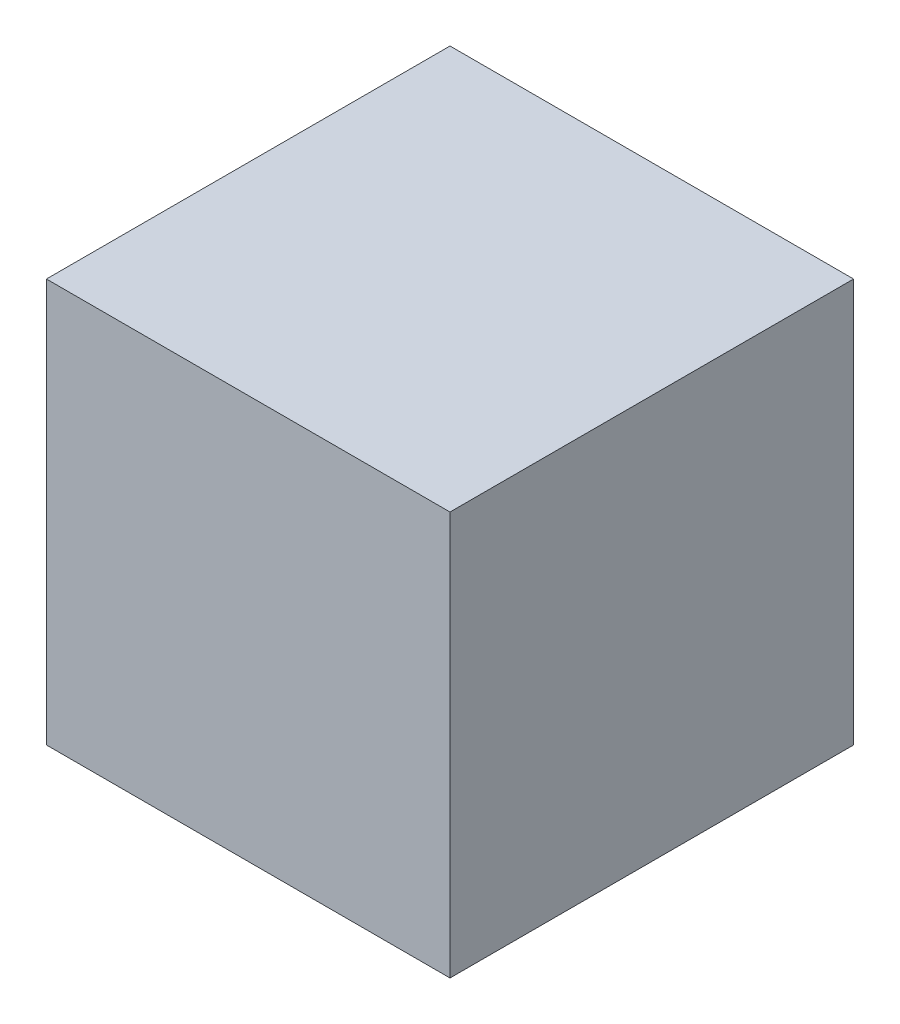
SolidWorks part; units mm, degrees
ref_plane "Front Plane" through (0, 0, 0) normal (0, 0, 1) x (1, 0, 0)
ref_plane "Top Plane" through (0, 0, 0) normal (0, 1, 0) x (1, 0, 0)
ref_plane "Right Plane" through (0, 0, 0) normal (1, 0, 0) x (0, 0, -1)
sketch "Sketch1" plane through (0, 0, 0) normal (1, 0, 0) x (0, 0, -1)
  line L1 (-309.88, -309.88) -> (309.88, -309.88)
  line L2 (-309.88, -309.88) -> (-309.88, 309.88)
  line L3 (-309.88, 309.88) -> (309.88, 309.88)
  line L4 (309.88, -309.88) -> (309.88, 309.88)
  line L5 (-309.88, -309.88) -> (309.88, 309.88) construction
  line L6 (-309.88, 309.88) -> (309.88, -309.88) construction
  point P0 (0, 0)
  dimension "Size" = 619.76
extrude "Boss-Extrude1" add sketch "Sketch1" along normal mid plane 619.76
equation "\"D1@Boss-Extrude1\" = \"Size@Sketch1\""
